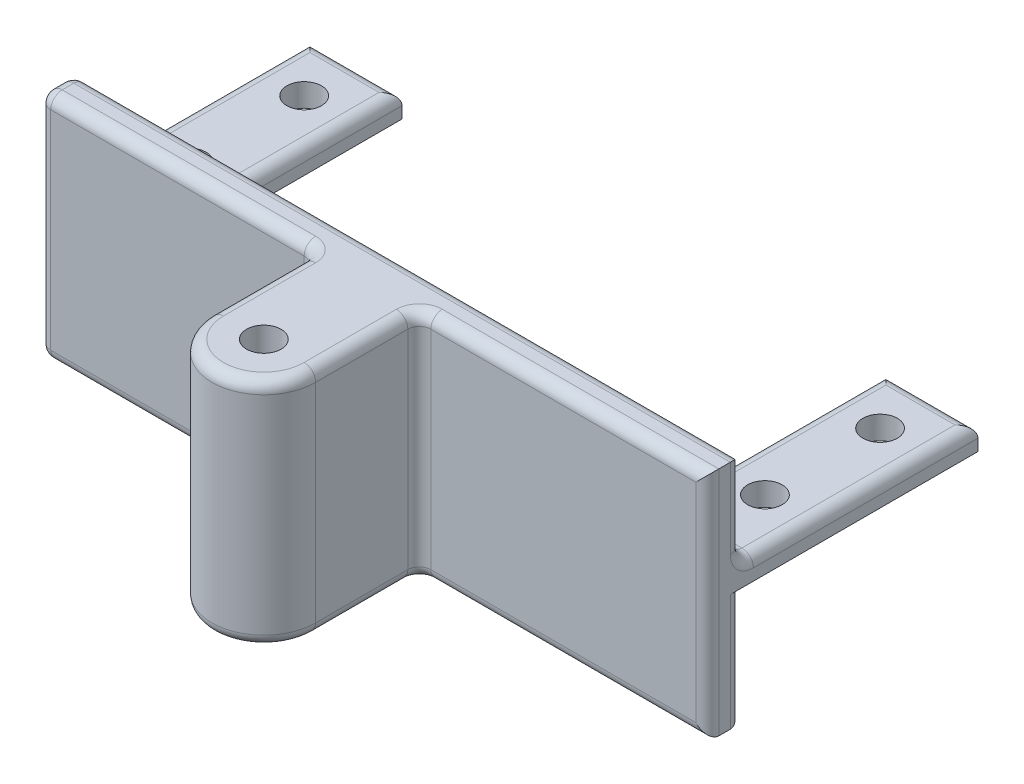
SolidWorks part; units mm, degrees
note: The reader was unsure of these and kept them because the rebuilt part matched: shared geometry of "Sketch1<3>", "Sketch1<4>".
ref_plane "Front Plane" through (0, 0, 0) normal (0, 0, 1) x (1, 0, 0)
ref_plane "Top Plane" through (0, 0, 0) normal (0, 1, 0) x (1, 0, 0)
ref_plane "Right Plane" through (0, 0, 0) normal (1, 0, 0) x (0, 0, -1)
sketch "Sketch1" plane through (0, 0, 0) normal (0, 1, 0) x (1, 0, 0)
  line L0 (-4.5, 20) -> (-4.5, 0) construction
  line L1 (0, 0) -> (41, 0)
  line L2 (0, 0) -> (0, 20)
  line L3 (0, 20) -> (41, 20)
  line L4 (41, 0) -> (41, 20)
  line L5 (0, 20) -> (-9, 20)
  line L6 (0, 20) -> (0, 0)
  line L7 (0, 0) -> (-9, 0)
  line L8 (-9, 20) -> (-9, 0)
  line L9 (41, 20) -> (50, 20)
  line L10 (41, 20) -> (41, 0)
  line L11 (41, 0) -> (50, 0)
  line L12 (50, 20) -> (50, 0)
  line L13 (-9, 10) -> (0, 10) construction
  line L14 (20.5, 20) -> (20.5, 0) construction
  line L15 (-8.5, 19.5) -> (-0.5, 19.5)
  line L16 (-8.5, 19.5) -> (-8.5, 0.5)
  line L17 (-8.5, 0.5) -> (-0.5, 0.5)
  line L18 (-0.5, 19.5) -> (-0.5, 0.5)
  line L19 (-8.5, 19.5) -> (-0.5, 0.5) construction
  line L20 (-8.5, 0.5) -> (-0.5, 19.5) construction
  line L21 (49.5, 0.5) -> (41.5, 0.5)
  line L22 (41.5, 19.5) -> (41.5, 0.5)
  line L23 (49.5, 19.5) -> (41.5, 19.5)
  line L24 (49.5, 19.5) -> (49.5, 0.5)
  line L25 (45.5, 20) -> (45.5, 0) construction
  line L26 (0, 0) -> (10, 0)
  line L27 (0, 0) -> (0, 10)
  line L28 (0, 10) -> (10, 10)
  line L29 (10, 0) -> (10, 10)
  line L30 (41, 10) -> (50, 10) construction
  circle A0 centre (10, 10) radius 1.5
  circle A1 centre (45.5, 15) radius 1.5
  circle A2 centre (45.5, 5) radius 1.5
  circle A3 centre (-4.5, 15) radius 1.5
  circle A4 centre (-4.5, 5) radius 1.5
  point P13 (-4.5, 10)
  point P35 (45.5, 10)
  dimension "D8" = 3
  dimension "D9" = 3
  dimension "D1" = 41
  dimension "D2" = 20
  dimension "D3" = 9
  dimension "D4" = 9
  dimension "D5" = 8
  dimension "D6" = 19
  dimension "D7" = 10
  dimension "D10" = 5
  dimension "D11" = 5
extrude "Boss-Extrude1" add sketch "Sketch1" along normal blind 2 contours L18 L15 L16 L17 | L21 L22 L23 L24
sketch "Sketch2" plane through (0, 0, 0) normal (0, 0, 1) x (1, 0, 0)
  line L0 (-8.5, 0) -> (49.5, 0)
  line L1 (-8.5, 0) -> (-8.5, 8)
  line L2 (49.5, 0) -> (49.5, 8)
  line L3 (-8.5, 8) -> (49.5, 8)
  line L4 (-8.5, 0) -> (49.5, 0)
  line L5 (-8.5, 0) -> (-8.5, -10)
  line L6 (49.5, 0) -> (49.5, -10)
  line L7 (-8.5, -10) -> (49.5, -10)
  dimension "D1" = 8
  dimension "D2" = 10
sketch "Sketch3" plane through (0, 0, -0.5) normal (0, 0, 1) x (1, 0, 0)
  line L0 (-8.5, 0) -> (49.5, 0)
  line L1 (-8.5, 0) -> (-8.5, 7.9449)
  line L2 (49.5, 0) -> (49.5, 7.9449)
  line L3 (-8.5, 7.9449) -> (49.5, 7.9449)
  line L4 (-8.5, 0) -> (49.5, 0)
  line L5 (-8.5, 0) -> (-8.5, -10.1326)
  line L6 (49.5, 0) -> (49.5, -10.1326)
  line L7 (-8.5, -10.1326) -> (49.5, -10.1326)
  line M1 (-8.5, 0) -> (-0.5, 0)
  line M2 (-0.5, 0) -> (-0.5, 2)
  line M3 (-0.5, 2) -> (-8.5, 2)
  line M4 (-8.5, 2) -> (-8.5, 0)
  dimension "D1" = 58
extrude "Boss-Extrude3" add sketch "Sketch3" along normal blind 4.5 contours L3 L1 L0 L2 M3 M2 | L5 L7 L6 L0 M1 | M4 M1 M2 M3
sketch "Sketch4" plane through (0, 0, 4) normal (0, 0, 1) x (1, 0, 0)
  line L0 (-8.5, -1.0938) -> (49.5, -1.0938) construction
  line L1 (-8.5, -10.1326) -> (-8.5, 7.9449) construction
  line L2 (49.5, -10.1326) -> (49.5, 7.9449) construction
  line L3 (20.5, 7.9449) -> (20.5, -10.1326) construction
  line L4 (-8.5, 7.9449) -> (49.5, 7.9449) construction
  line L5 (-8.5, -10.1326) -> (49.5, -10.1326) construction
  line L6 (15.5, -10.1326) -> (15.5, 7.9449)
  line L7 (15.5, -10.1326) -> (24.5, -10.1326)
  line L8 (15.5, 7.9449) -> (24.5, 7.9449)
  line L9 (24.5, -10.1326) -> (24.5, 7.9449)
  line L10 (15.5, -10.1326) -> (24.5, 7.9449) construction
  line L11 (15.5, 7.9449) -> (24.5, -10.1326) construction
  point P13 (20, -1.0938)
  dimension "D1" = 9
extrude "Boss-Extrude4" add sketch "Sketch4" along normal blind 9 contours L6 L7 L9 L8
sketch "Sketch5" plane through (0, 7.9449, 0) normal (0, 1, 0) x (1, 0, 0)
  line L0 (15.5, -13) -> (18.5, -13)
  line L1 (24.5, -13) -> (21.5, -13)
  arc A0 (15.5, -13) -> (24.5, -13) centre (20, -13) ccw
  circle A1 centre (20, -13) radius 1.5
  line M5 (15.5, -13) -> (24.5, -13)
  dimension "D1" = 3
extrude "Boss-Extrude5" add sketch "Sketch5" against normal through all contours A1 A0 M5
sketch "Sketch6" plane through (0, 7.9449, 0) normal (0, 1, 0) x (1, 0, 0)
  circle A0 centre (20, -13) radius 1.5
extrude "Cut-Extrude1" cut sketch "Sketch6" against normal through all
extrude "Cut-Extrude2" cut sketch "Sketch1<3>" along normal through all contours A1
sketch "Sketch1<3>" plane through (0, 0, 0) normal (0, 1, 0) x (1, 0, 0) same geometry as "Sketch1"
extrude "Cut-Extrude3" cut sketch "Sketch1<4>" along normal through all contours A2
sketch "Sketch1<4>" plane through (0, 0, 0) normal (0, 1, 0) x (1, 0, 0) same geometry as "Sketch1"
sketch "Sketch12" plane through (0, 0, -0.5) normal (0, 0, -1) x (-1, 0, 0)
  line L1 (-49.5, 0) -> (8.5, 0)
  line L2 (-49.5, 0) -> (-49.5, -10.1326)
  line L3 (-49.5, -10.1326) -> (8.5, -10.1326)
  line L4 (8.5, 0) -> (8.5, -10.1326)
  line L5 (-41.5, 2) -> (0.5, 2)
  line L6 (-41.5, 2) -> (-41.5, 0)
  line L7 (-41.5, 0) -> (0.5, 0)
  line L8 (0.5, 2) -> (0.5, 0)
  line L9 (-49.5, 7.9449) -> (8.5, 7.9449)
  line L10 (-49.5, 7.9449) -> (-49.5, 2)
  line L11 (-49.5, 2) -> (8.5, 2)
  line L12 (8.5, 7.9449) -> (8.5, 2)
  line M13 (-49.5, 2) -> (-41.5, 2)
  line M14 (-41.5, 2) -> (-41.5, 0)
  line M15 (-41.5, 0) -> (-49.5, 0)
  line M16 (-49.5, 0) -> (-49.5, -10.1326)
  line M17 (-49.5, -10.1326) -> (8.5, -10.1326)
  line M18 (8.5, -10.1326) -> (8.5, 0)
  line M19 (8.5, 0) -> (0.5, 0)
  line M20 (0.5, 0) -> (0.5, 2)
  line M21 (0.5, 2) -> (8.5, 2)
  line M22 (8.5, 2) -> (8.5, 7.9449)
  line M23 (8.5, 7.9449) -> (-49.5, 7.9449)
  line M24 (-49.5, 7.9449) -> (-49.5, 2)
extrude "Cut-Extrude5" cut sketch "Sketch12" against normal blind 1.5 contours L5 M13 M21 M22 M23 M24 | L5 L1 M14 M20 | L1 M15 M16 M17 M18 M19
sketch "Sketch14" plane through (0, 7.9449, 0) normal (0, 1, 0) x (1, 0, 0)
  line L1 (-8.5, -1) -> (49.5, -1)
  line L2 (-8.5, -1) -> (-8.5, -4)
  line L3 (-8.5, -4) -> (49.5, -4)
  line L4 (49.5, -1) -> (49.5, -4)
  line L5 (15.5, -4) -> (24.5, -4)
  line L6 (15.5, -4) -> (15.5, -13)
  line L7 (15.5, -13) -> (24.5, -13)
  line L8 (24.5, -4) -> (24.5, -13)
  circle A0 centre (20, -13) radius 1.5
  circle A1 centre (20, -13) radius 4.5
  circle M1 centre (20, -13) radius 1.5
  line M2 (49.5, -4) -> (49.5, -1)
  line M3 (49.5, -1) -> (-8.5, -1)
  line M4 (-8.5, -1) -> (-8.5, -4)
  line M5 (-8.5, -4) -> (15.5, -4)
  line M6 (15.5, -4) -> (15.5, -13)
  arc M7 (15.5, -13) -> (24.5, -13) centre (20, -13) ccw
  line M8 (24.5, -13) -> (24.5, -4)
  line M9 (24.5, -4) -> (49.5, -4)
extrude "Boss-Extrude6" add sketch "Sketch14" along normal blind 2 contours L3 M5 M9 M2 M3 M4 | A1 L3 M8 M6 | L7 A1 M1 | L7 M7 M1
fillet "Fillet1" radius 1 32 edges at (-0.5, 2, -9.25) (45.5, 2, 1) (49.5, 5.9725, 1) (-8.5, 5.9725, 1) (-4.5, 2, 1) (-0.5, 1, 1) (-8.5, -5.0663, 1) (20.5, -10.1326, 1) (49.5, -5.0663, 1) (41.5, 1, 1) (20, 9.9449, 17.5) (24.5, 9.9449, 8.5) (37, 9.9449, 4) (20.5, 9.9449, 1) (-8.5, 9.9449, 2.5) (-4.5, 2, -19.5) (3.5, 9.9449, 4) (15.5, 9.9449, 8.5) (-8.5, 2, -9.25) (-8.5, -0.0938, 4) (-8.5, -10.1326, 2.5) (3.5, -10.1326, 4) (49.5, -0.0938, 4) (49.5, 2, -9.25) (45.5, 2, -19.5) (41.5, 2, -9.25) (37, -10.1326, 4) (15.5, -10.1326, 8.5) (24.5, -0.0938, 4) (24.5, -10.1326, 8.5) (15.5, -0.0938, 4) (20, -10.1326, 17.5)
